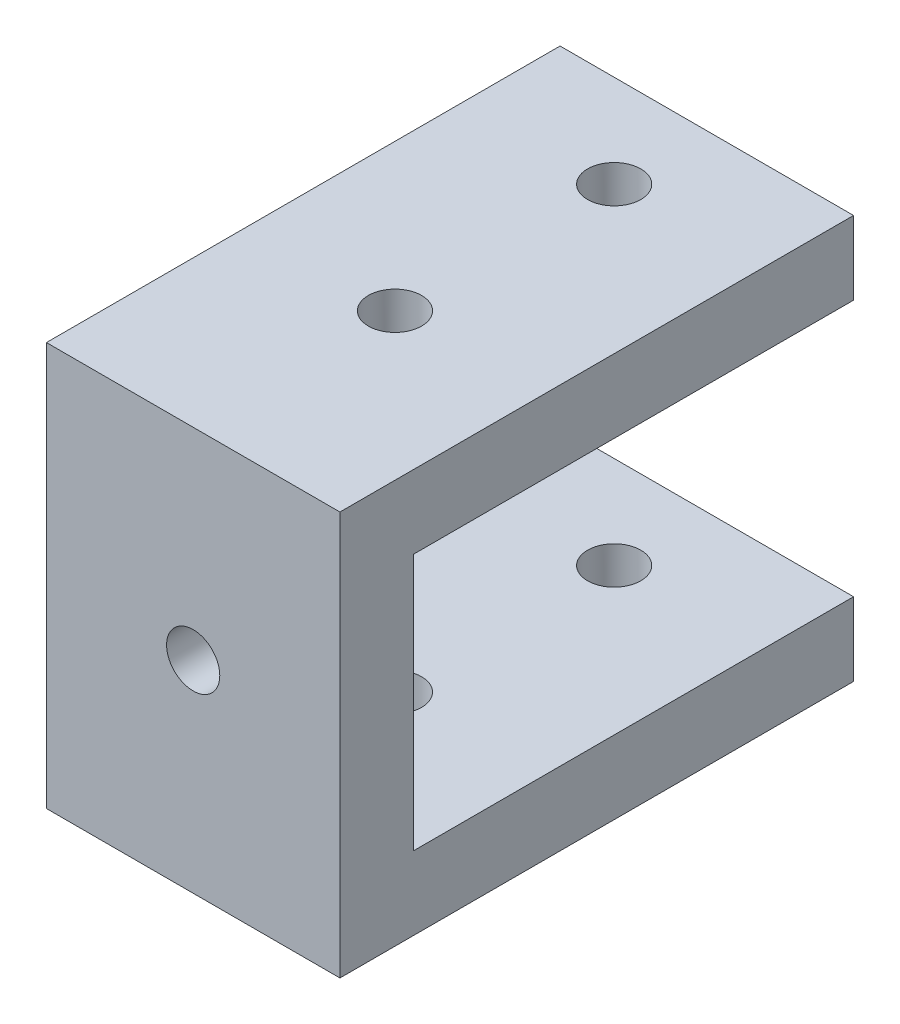
SolidWorks part; units mm, degrees
ref_plane "Front Plane" through (0, 0, 0) normal (0, 0, 1) x (1, 0, 0)
ref_plane "Top Plane" through (0, 0, 0) normal (0, 1, 0) x (1, 0, 0)
ref_plane "Right Plane" through (0, 0, 0) normal (1, 0, 0) x (0, 0, -1)
sketch "Sketch1" plane through (0, 0, 0) normal (1, 0, 0) x (0, 0, -1)
  line L0 (0, 8.89) -> (0, -8.89)
  line L1 (0, -8.89) -> (30.48, -8.89)
  line L2 (30.48, -8.89) -> (30.48, -13.97)
  line L3 (30.48, -13.97) -> (-5.08, -13.97)
  line L4 (-5.08, -13.97) -> (-5.08, 13.97)
  line L5 (-5.08, 13.97) -> (30.48, 13.97)
  line L6 (30.48, 13.97) -> (30.48, 8.89)
  line L7 (30.48, 8.89) -> (0, 8.89)
  point P8 (0, 0)
  dimension "D1" = 5.08
  dimension "D2" = 5.08
  dimension "D3" = 30.48
  dimension "D4" = 17.78
extrude "Boss-Extrude1" add sketch "Sketch1" along normal blind 20.32
sketch "Sketch2" plane through (0, 0, 5.08) normal (0, 0, 1) x (1, 0, 0)
  line L1 (20.32, 13.97) -> (20.32, -13.97) construction
  circle A0 centre (10.16, 0) radius 1.8415
  dimension "D1" = 3.683
  dimension "D2" = 10.16
extrude "Cut-Extrude1" cut sketch "Sketch2" against normal up to next
sketch "Sketch3" plane through (0, 13.97, 0) normal (0, 1, 0) x (1, 0, 0)
  line L0 (20.32, -5.08) -> (0, -5.08) construction
  line L1 (20.32, 30.48) -> (20.32, -5.08) construction
  line L2 (20.32, 30.48) -> (0, 30.48) construction
  circle A0 centre (10.16, 8.89) radius 1.8415
  circle A1 centre (10.16, 24.0665) radius 1.8415
  dimension "D1" = 3.683
  dimension "D2" = 13.97
  dimension "D3" = 10.16
  dimension "D4" = 6.4135
extrude "Cut-Extrude2" cut sketch "Sketch3" against normal through all and the other way through all
